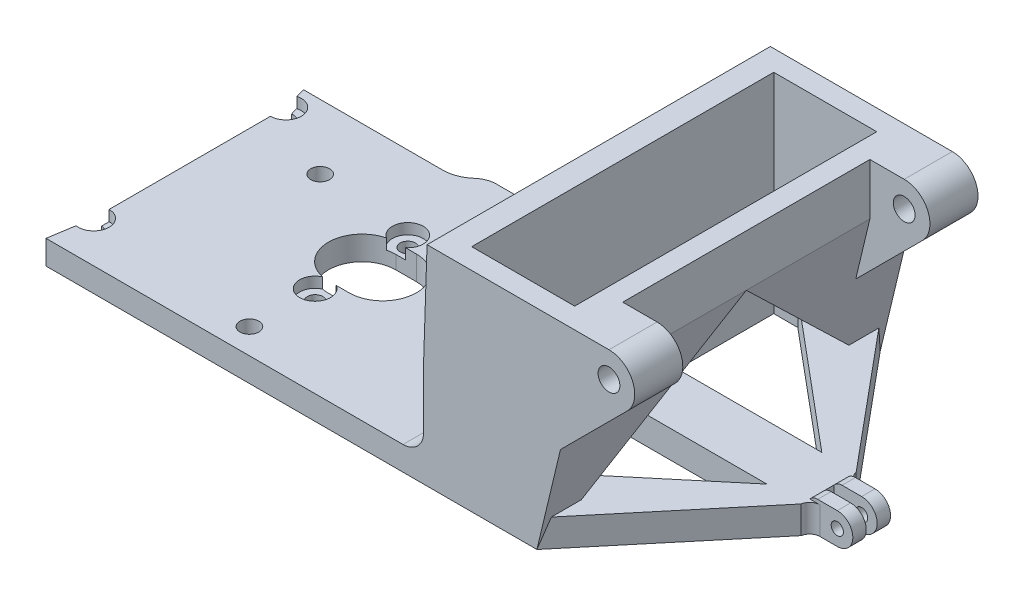
SolidWorks part; units mm, degrees
note: The reader was unsure of these and kept them because the rebuilt part matched: shared geometry of "Sketch29<3>".
ref_plane "Front Plane" through (0, 0, 0) normal (0, 0, 1) x (1, 0, 0)
ref_plane "Top Plane" through (0, 0, 0) normal (0, 1, 0) x (1, 0, 0)
ref_plane "Right Plane" through (0, 0, 0) normal (1, 0, 0) x (0, 0, -1)
sketch "Sketch1" plane through (0, 0, 0) normal (0, 1, 0) x (1, 0, 0)
  line L1 (-35, 60) -> (80, 60)
  line L2 (-35, 60) -> (-35, -40)
  line L3 (-35, -40) -> (80, -40)
  line L4 (80, 60) -> (80, -40)
  point P0 (0, 0)
  dimension "D1" = 115
  dimension "D2" = 100
  dimension "D3" = 40
  dimension "D4" = 35
extrude "Extrude1" add sketch "Sketch1" along normal blind 7
sketch "Sketch2" plane through (0, 0, 0) normal (0, 1, 0) x (1, 0, 0)
  line L0 (-28.109, -30.4503) -> (-28.109, 28) construction
  line L1 (-35, 60) -> (-35, -40) construction
  line L2 (-47.7977, 0) -> (51.3963, 0) construction
  line L3 (21.891, -18.2702) -> (21.891, 18.8238) construction
  line L4 (5, -25.5364) -> (5, 23.1606) construction
  line L5 (-13, -30.4503) -> (-13, 32.9416) construction
  line L6 (38.782, 10.2941) -> (38.782, -21.3756) construction
  line L7 (-6.2548, 16.1175) -> (21.891, -0.1325) construction
  line L8 (21.891, -13.5) -> (-7.9984, -13.5) construction
  line L9 (21.891, 10) -> (27.891, 10)
  line L10 (21.891, -9.5966) -> (27.891, -9.5966)
  line L11 (50.0369, 16.1175) -> (21.891, -0.1325) construction
  line L12 (21.891, -0.1325) -> (21.891, -32.6325) construction
  circle A0 centre (-6.2548, 16.1175) radius 2.75
  circle A1 centre (50.0369, 16.1175) radius 2.75
  circle A2 centre (-28.109, -28) radius 2.25
  circle A3 centre (-28.109, 28) radius 2.25
  circle A4 centre (21.891, -32.6325) radius 2.75
  arc A5 (21.891, 10) -> (21.891, -9.5966) centre (21.891, 0.2017) ccw
  circle A6 centre (21.891, -13.5) radius 2.25
  circle A7 centre (21.891, 13.5) radius 2.25
  arc A8 (27.891, 10) -> (27.891, -9.5966) centre (27.891, 0.2017) cw
  circle A9 centre (21.891, -0.1325) radius 32.5 construction
  point P10 (48.2117, 18.8238)
  point P16 (0, 0)
  dimension "D4" = 16.891
  dimension "D5" = 28
  dimension "D6" = 4.5
  dimension "D7" = 50
  dimension "D10" = 65
  dimension "D11" = 120
  dimension "D12" = 4.5
  dimension "D13" = 4.5
  dimension "D18" = 5.5
  dimension "D19" = 5.5
  dimension "D21" = 10
  dimension "D23" = 6
  dimension "D3" = 4.5
  dimension "D14" = 5.5
  dimension "D16" = 120
  dimension "D1" = 6.891
  dimension "D2" = 28
  dimension "D8" = 13.5
  dimension "D9" = 13.5
  dimension "D15" = 40
  dimension "D20" = 18
extrude "Extrude7" cut sketch "Sketch2" along normal blind 7
hole_wizard "CBORE for M4 Pan Head Machine Screw2" positions "3DSketch10" profile "Sketch14" counterbore size "M4" standard "Ansi Metric" end condition through all
sketch3d "3DSketch10"
  line L0 (-28.109, 7, -28) -> (-28.109, 0, -28) construction
  line L1 (21.891, 7, -13.5) -> (21.891, 0, -13.5) construction
  line L2 (21.891, 7, 13.5) -> (21.891, 0, 13.5) construction
  line L3 (-28.109, 7, 28) -> (-28.109, 0, 28) construction
  point P0 (-28.109, 7, -28)
  point P4 (21.891, 7, -13.5)
  point P8 (21.891, 7, 13.5)
  point P12 (-28.109, 7, 28)
sketch "Sketch14" plane through (-28.109, 7, -28) normal (1, 0, 0) x (0, 0, 1)
  line L0 (0, 0) -> (0, 7)
  line L1 (0, 7) -> (2.25, 7)
  line L3 (2.25, 7) -> (2.25, 3.1)
  line L4 (2.25, 3.1) -> (4.5, 3.1)
  line L5 (4.5, 3.1) -> (4.5, 0)
  line L7 (4.5, 0) -> (0, 0)
  line L11 (0, -6.35) -> (0, 107.95) construction
  dimension "Thru Hole Dia." = 4.5
  dimension "Thru Hole Depth" = 7
  dimension "C'Bore Dia." = 9
  dimension "C'Bore Depth" = 3.1
sketch "Sketch18" plane through (0, 7, 0) normal (0, 1, 0) x (1, 0, 0)
  line L0 (26.1303, -32.6325) -> (16.7823, -32.6325) construction
  line L1 (21.891, 39.3001) -> (21.891, 26.9019) construction
  line L2 (30, 39.3001) -> (21.891, 39.3001)
  line L4 (-30, -40) -> (-35, -40)
  line L5 (-35, 60) -> (-35, -40) construction
  line L6 (-35, 35) -> (-35, 60)
  line L7 (-35, 60) -> (80, 60)
  line L8 (80, 60) -> (80, 39.3001)
  line L9 (-28.109, 28) -> (-28.109, -28)
  line L10 (-28.109, -28) -> (-30, -40)
  line L11 (-35, -40) -> (80, -40) construction
  line L12 (-30, 35) -> (15.4327, 35)
  line L13 (-35, -40) -> (-35, 35)
  line L14 (-28.109, 28) -> (-30, 35)
  line L15 (35, 44.3001) -> (35, 60)
  arc A0 (21.891, 39.3001) -> (15.4327, 35) centre (21.891, 32.3001) ccw
  arc A1 (35, 44.3001) -> (30, 39.3001) centre (30, 44.3001) cw
  circle M1 centre (-28.109, 28) radius 4.5
  circle M4 centre (-28.109, -28) radius 4.5
  line M8 (-35, 60) -> (-35, -40)
  line M9 (-35, -40) -> (80, -40)
  dimension "D1" = 7
  dimension "D4" = 5
  dimension "D2" = 45
  dimension "D3" = 5
extrude "Extrude9" cut sketch "Sketch18" against normal through all contours A1 L15 L7 L10 L9 L14 L12 A0 L2 M8 M9 M4 M1 | L9 L14 M1 | L10 L9 M4
fillet "Fillet1" radius 10 2 edges at (35, 3.5, -60) (15.4327, 3.5, -35)
sketch "Sketch19" plane through (80, 0, 0) normal (1, 0, 0) x (0, 0, -1)
  line L0 (-40, 7) -> (-40, 0) construction
  line L1 (60, 0) -> (-40, 0)
  line L2 (60, 0) -> (60, 60.9)
  line L3 (60, 60.9) -> (-40, 60.9)
  line L4 (-40, 0) -> (-40, 60.9)
  dimension "D1" = 60.9
extrude "Boss-Extrude1" add sketch "Sketch19" along normal blind 8
sketch "Sketch20" plane through (0, 0, -60) normal (0, 0, -1) x (-1, 0, 0)
  line L0 (-88, 0) -> (-113, 0)
  line L1 (-113, 0) -> (-124, 45.9)
  line L2 (-124, 45.9) -> (-124, 60.9)
  line L3 (-124, 60.9) -> (-88, 60.9)
  line L10 (-88, 0) -> (-45, 0)
  line L11 (-45, 0) -> (-45, 7)
  line L12 (-45, 7) -> (-80, 7)
  line L13 (-80, 7) -> (-80, 60.9)
  line L14 (-80, 60.9) -> (-88, 60.9)
  line L15 (-88, 60.9) -> (-88, 0)
  line L16 (-88, 0) -> (-45, 0)
  line L17 (-45, 0) -> (-45, 7)
  line L18 (-45, 7) -> (-80, 7)
  line L19 (-80, 7) -> (-80, 60.9)
  line L20 (-80, 60.9) -> (-88, 60.9)
  dimension "D1" = 15
  dimension "D2" = 36
  dimension "D3" = 25
  dimension "D4" = 0
extrude "Boss-Extrude2" add sketch "Sketch20" against normal blind 6
sketch "Sketch21" plane through (0, 0, 40) normal (0, 0, 1) x (1, 0, 0)
  line L5 (88, 60.9) -> (88, 0)
  line L6 (88, 0) -> (113, 0)
  line L7 (113, 0) -> (124, 45.9)
  line L8 (124, 45.9) -> (124, 60.9)
  line L9 (124, 60.9) -> (88, 60.9)
  line L10 (88, 60.9) -> (88, 0)
  line L11 (88, 0) -> (113, 0)
  line L12 (113, 0) -> (124, 45.9)
  line L13 (124, 45.9) -> (124, 60.9)
  line L14 (124, 60.9) -> (88, 60.9)
  dimension "D1" = 0
extrude "Boss-Extrude3" add sketch "Sketch21" against normal blind 6
sketch "Sketch22" plane through (0, 0, -54) normal (0, 0, 1) x (1, 0, 0)
  line L0 (88, 60.9) -> (124, 60.9) construction
  line L1 (124, 45.9) -> (118, 45.9)
  line L2 (124, 45.9) -> (124, 60.9)
  line L3 (124, 60.9) -> (118, 60.9)
  line L4 (118, 45.9) -> (118, 60.9)
  dimension "D1" = 6
extrude "Boss-Extrude4" add sketch "Sketch22" along normal up to surface (88 mm away) up to face at (107.4, 33.54, 34)
sketch "Sketch23" plane through (106.8626, -25.6098, 0) normal (0.9725, -0.2331, 0) x (0, 0, -1)
  line L0 (54, 29.5346) -> (10, 73.5346)
  line L1 (54, 73.5346) -> (54, 26.3349) construction
  line L2 (-34, 73.5346) -> (54, 73.5346) construction
  line L3 (10, 73.5346) -> (-34, 29.5346)
  line L4 (-34, 26.3349) -> (-34, 73.5346) construction
  line L5 (-34, 26.3349) -> (-34, 73.5346)
  line L6 (-34, 73.5346) -> (54, 73.5346)
  line L7 (54, 73.5346) -> (54, 26.3349)
  line M4 (54, 73.5346) -> (54, 26.3349)
  dimension "D1" = 45
extrude "Boss-Extrude5" add sketch "Sketch23" against normal up to vertex (5.8348 mm away) contours L6 L0 M4 | L6 L5 L3
sketch "Sketch25" plane through (0, 0, -60) normal (0, 0, -1) x (-1, 0, 0)
  line L0 (-124, 60.9) -> (-80, 60.9) construction
  line L1 (-124, 45.9) -> (-134, 45.9)
  line L2 (-124, 45.9) -> (-124, 60.9)
  line L3 (-124, 60.9) -> (-134, 60.9)
  line L4 (-139.3033, 48.0967) -> (-119.869, 28.6624)
  line L5 (-124, 45.9) -> (-113, 0) construction
  line L6 (-119.869, 28.6624) -> (-124, 45.9)
  line L7 (-113, 0) -> (-45, 0) construction
  arc A0 (-134, 60.9) -> (-134, 45.9) centre (-134, 53.4) ccw
  circle A1 centre (-134, 53.4) radius 3.175
  line M8 (-124, 60.9) -> (-124, 45.9)
  line M9 (-124, 45.9) -> (-113, 0)
  dimension "D2" = 6.35
  dimension "D1" = 10
  dimension "D3" = 45
extrude "Boss-Extrude6" add sketch "Sketch25" against normal blind 14 contours L3 A0 L1 A1 M8 | A0 L4 L1 M9
sketch "Sketch26" plane through (0, 0, 40) normal (0, 0, 1) x (1, 0, 0)
  line L4 (134, 60.9) -> (124, 60.9)
  line L5 (124, 60.9) -> (124, 45.9)
  line L6 (124, 45.9) -> (119.869, 28.6624)
  line L7 (119.869, 28.6624) -> (139.3033, 48.0967)
  line L8 (134, 60.9) -> (124, 60.9)
  line L9 (124, 60.9) -> (124, 45.9)
  line L10 (124, 45.9) -> (119.869, 28.6624)
  line L11 (119.869, 28.6624) -> (139.3033, 48.0967)
  circle A0 centre (134, 53.4) radius 3.175 construction
  arc A1 (139.3033, 48.0967) -> (134, 60.9) centre (134, 53.4) ccw
  arc A2 (139.3033, 48.0967) -> (134, 60.9) centre (134, 53.4) ccw
  circle A3 centre (134, 53.4) radius 3.175
  dimension "D1" = 0
extrude "Boss-Extrude7" add sketch "Sketch26" against normal blind 14
fillet "Fillet2" radius 6 1 edges at (80, 7, -10)
sketch "Sketch27" plane through (0, 0, 0) normal (0, -1, 0) x (1, 0, 0)
  line L0 (113, 34) -> (113, 40) construction
  line L1 (88, -2) -> (148, -2)
  line L2 (88, -2) -> (88, -18)
  line L3 (88, -18) -> (148, -18)
  line L4 (148, -2) -> (148, -18)
  line L5 (113, -54) -> (113, -60) construction
  line L6 (88, 34) -> (88, -54) construction
  line L7 (113, -60) -> (45, -60) construction
  line L8 (-30, 40) -> (113, 40) construction
  line L9 (113, 34) -> (113, 40)
  line L10 (113, -54) -> (113, -60)
  line L11 (88, 34) -> (88, -54)
  line L12 (113, -60) -> (45, -60)
  line L13 (-30, 40) -> (113, 40)
  line L14 (88, -10) -> (148, -10) construction
  line L15 (113, 40) -> (148, -2)
  line L16 (148, -18) -> (113, -60)
  line L17 (138, -18) -> (95, -54)
  line L18 (113, -54) -> (88, -54) construction
  line L19 (138, -2) -> (95, 34)
  line L20 (88, 34) -> (113, 34) construction
  line L21 (88, 34) -> (113, 34)
  line L22 (113, -54) -> (88, -54)
  line M17 (113, -60) -> (113, -54)
  line M18 (113, -54) -> (88, -54)
  line M19 (88, -54) -> (88, 34)
  line M20 (88, 34) -> (113, 34)
  line M21 (113, 34) -> (113, 40)
  dimension "D1" = 60
  dimension "D2" = 16
  dimension "D3" = 7
  dimension "D4" = 7
  dimension "D5" = 10
extrude "Boss-Extrude8" add sketch "Sketch27" against normal blind 4 contours L19 L1 L15 M21 M20 | L11 L14 L4 L1 | L3 L17 L16 M18 M17 | L14 L3 L4 M19
sketch "Sketch28" plane through (0, 4, 0) normal (0, 1, 0) x (1, 0, 0)
  line L0 (148, 13.0819) -> (115.5747, 51.9922)
  line L1 (148, 2) -> (148, 18) construction
  line L2 (111.0785, -37.3877) -> (148, 6.9181)
  line L3 (145, 21.6) -> (145, -1.6)
  line L14 (113.9586, 58.8497) -> (113.9586, 53.0864)
  line L15 (110.0385, 54) -> (95, 54)
  line L16 (95, 54) -> (138, 18)
  line L17 (138, 18) -> (88, 18)
  line L18 (88, 18) -> (88, 2)
  line L19 (88, 2) -> (138, 2)
  line L20 (138, 2) -> (95, -34)
  line L21 (95, -34) -> (110.0385, -34)
  line L22 (113.9586, -33.0864) -> (113.9586, -38.8497)
  line L23 (113.9586, -38.8497) -> (148, 2)
  line L24 (148, 2) -> (148, 18)
  line L25 (148, 18) -> (113.9586, 58.8497)
  line L26 (113.9586, 58.8497) -> (113.9586, 53.0864)
  line L27 (110.0385, 54) -> (95, 54)
  line L28 (95, 54) -> (138, 18)
  line L29 (138, 18) -> (88, 18)
  line L30 (88, 18) -> (88, 2)
  line L31 (88, 2) -> (138, 2)
  line L32 (138, 2) -> (95, -34)
  line L33 (95, -34) -> (110.0385, -34)
  line L34 (113.9586, -33.0864) -> (113.9586, -38.8497)
  line L35 (113.9586, -38.8497) -> (148, 2)
  line L36 (148, 2) -> (148, 18)
  line L37 (148, 18) -> (113.9586, 58.8497)
  line L42 (113.9586, 53.0864) -> (110.0385, 54)
  line L43 (113.9586, 53.0864) -> (110.0385, 54)
  line L44 (110.0385, -34) -> (113.9586, -33.0864)
  line L45 (110.0385, -34) -> (113.9586, -33.0864)
  line M15 (113.9586, 58.8497) -> (113.9586, 53.0864)
  line M23 (113.9586, -33.0864) -> (113.9586, -38.8497)
  line M24 (113.9586, -38.8497) -> (148, 2)
  line M25 (148, 2) -> (148, 18)
  line M26 (148, 18) -> (113.9586, 58.8497)
  dimension "D2" = 3
  dimension "D1" = 0
extrude "Boss-Extrude9" add sketch "Sketch28" along normal blind 4 contours L0 M25 M26 M15 | L2 M23 M24 M25 | L3 L0 M26 M25 | L0 L3 L2 M25 | L2 L3 M24 M25
ref_plane "Plane1" through (0, 0, -10) normal (0, 0, 1) x (1, 0, 0)
sketch "Sketch29" plane through (0, 0, -10) normal (0, 0, 1) x (1, 0, 0)
  line L0 (148, 9.06) -> (148, 0)
  line L2 (148, 9.06) -> (156, 9.06)
  line L3 (148, 9.06) -> (148, 0)
  line L4 (148, 0) -> (156, 0)
  line L5 (156, 9.06) -> (156, 0) construction
  circle A0 centre (156, 4.53) radius 4.53
  circle A1 centre (156, 4.53) radius 1.778
  dimension "D3" = 3.556
  dimension "D1" = 9.06
  dimension "D2" = 8
extrude "Boss-Extrude10" add sketch "Sketch29" along normal mid plane 11 contours L5 A0 A1 | A0 L5 A1 | A0 L2 L0 L4
extrude "Cut-Extrude1" cut sketch "Sketch29<3>" against normal mid plane 3.2 contours A0 L2 L0 L4 | L5 A0 A1 | A0 L5 A1
sketch "Sketch29<3>" plane through (0, 0, -10) normal (0, 0, 1) x (1, 0, 0) same geometry as "Sketch29"
fillet "Fillet3" radius 3 4 edges at (148, 9.06, -6.45) (148, 9.06, -13.55) (148, 4, -15.5) (148, 4, -4.5)
sketch "Sketch30" plane through (0, 0, 0) normal (0, -1, 0) x (1, 0, 0)
  line L0 (43.1611, -22.3029) -> (50.0369, -16.1175) construction
  line L1 (32.9411, -22.3029) -> (43.1611, -22.3029)
  line L2 (32.9411, -22.3029) -> (32.9411, -34.3429)
  line L3 (32.9411, -34.3429) -> (43.1611, -34.3429)
  line L4 (43.1611, -22.3029) -> (43.1611, -34.3429)
  line L5 (32.1611, -35.9029) -> (43.1611, -35.9029)
  line L6 (32.1611, -35.9029) -> (32.1611, -44.9029)
  line L7 (32.1611, -44.9029) -> (43.1611, -44.9029)
  line L8 (43.1611, -35.9029) -> (43.1611, -44.9029)
  line L9 (50.0369, -16.1175) -> (43.1611, -16.1175) construction
  line L10 (43.1611, -16.1175) -> (43.1611, -22.3029) construction
  dimension "D1" = 10.22
  dimension "D2" = 12.04
  dimension "D3" = 1.56
  dimension "D4" = 9
  dimension "D5" = 11
  dimension "D6" = 6.1854
  dimension "D7" = 6.8758
extrude "Cut-Extrude2" cut sketch "Sketch30" against normal through all
sketch "Sketch31" plane through (0, 0, -60) normal (0, 0, -1) x (-1, 0, 0)
  line L0 (-80, 60.9) -> (-81, 60.9)
  line L1 (-134, 60.9) -> (-80, 60.9) construction
  line L2 (-81, 60.9) -> (-80, 30.9)
  line L3 (-80, 13) -> (-80, 60.9) construction
  line L4 (-80, 30.9) -> (-80, 60.9)
  dimension "D1" = 30
  dimension "D2" = 1
extrude "Cut-Extrude3" cut sketch "Sketch31" against normal up to next
